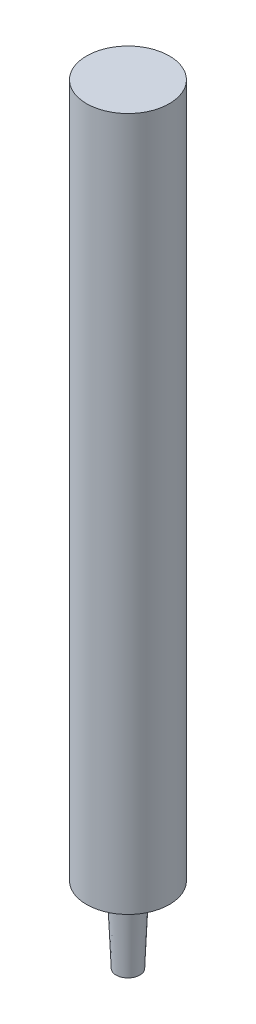
SolidWorks part; units mm, degrees
ref_plane "Front Plane" through (0, 0, 0) normal (0, 0, 1) x (1, 0, 0)
ref_plane "Top Plane" through (0, 0, 0) normal (0, 1, 0) x (1, 0, 0)
ref_plane "Right Plane" through (0, 0, 0) normal (1, 0, 0) x (0, 0, -1)
ref_axis "Axis1" through (-33.0333, 0, 0) along (1, 0, 0)
ref_axis "Axis2" through (0, 24.5224, 0) along (0, -1, 0)
ref_axis "Axis3" through (0, 0, -52.9538) along (0, 0, 1)
sketch "Sketch2" plane through (0, 0, 0) normal (0, 0, 1) x (1, 0, 0)
  line L8 (0, 60.5) -> (0, -60.5)
  line L9 (0, -60.5) -> (2.7, -60.5)
  line L10 (2.7, -60.5) -> (3.275, -46.35)
  line L11 (3.275, -46.35) -> (9.44, -42.5)
  line L14 (9.44, -42.5) -> (9.44, 60.5)
  line L18 (0, 60.5) -> (0, 122)
  line L19 (0, 122) -> (9.44, 122)
  line L20 (9.44, 122) -> (9.44, 60.5)
  dimension "D1" = 121
  dimension "D2" = 2.7
  dimension "D3" = 14.15
  dimension "D4" = 61.5
  dimension "D6" = 9.44
  dimension "D7" = 3.275
  dimension "D8" = 18
revolve "Revolve1" add sketch "Sketch2" angle 360 about L8
scale "Scale1" scale about origin uniform scaling no x scale factor 1.05 y scale factor 1.01 z scale factor 1.05
